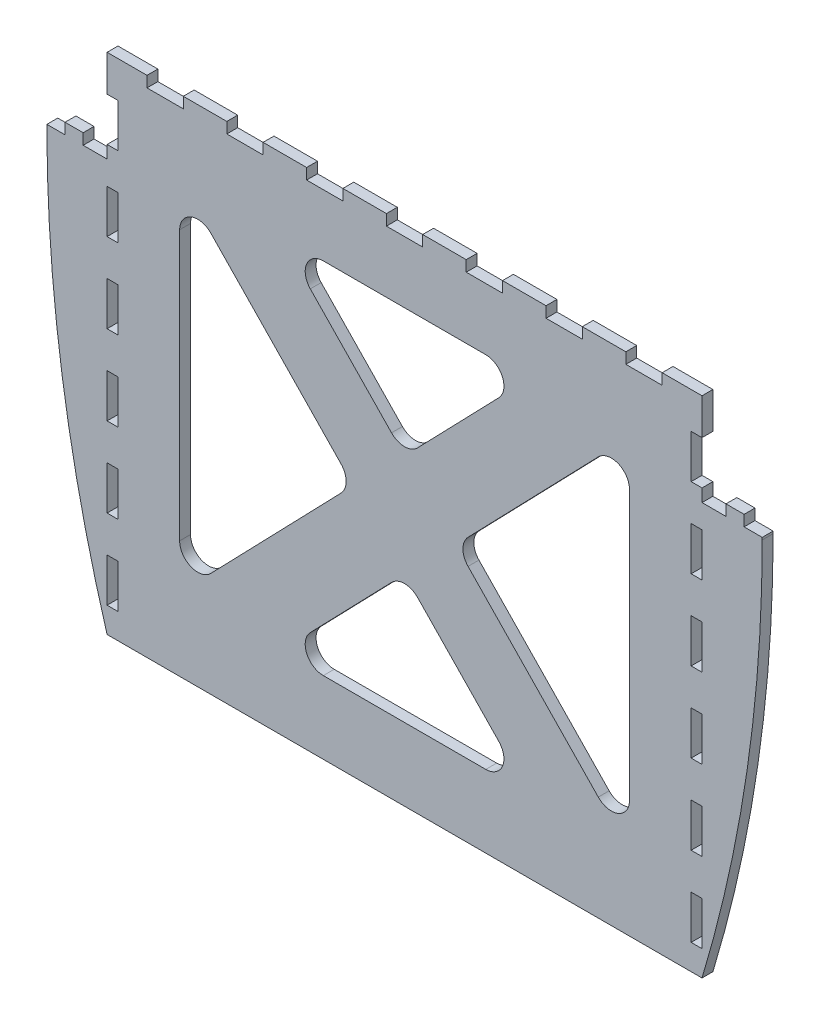
SolidWorks part; units mm, degrees
material "birch 3mm plywood"
ref_plane "Front Plane" through (0, 0, 0) normal (0, 0, 1) x (1, 0, 0)
ref_plane "Top Plane" through (0, 0, 0) normal (0, 1, 0) x (1, 0, 0)
ref_plane "Right Plane" through (0, 0, 0) normal (1, 0, 0) x (0, 0, -1)
sketch "Sketch1" plane through (0, 0, 152) normal (0, 0, 1) x (1, 0, 0)
  line L1 (-82, 69.5) -> (82, 69.5)
  line L2 (-82, 69.5) -> (-82, 44)
  line L3 (-82, -69.5) -> (82, -69.5)
  line L4 (82, 69.5) -> (82, 44)
  line L6 (-62, -37.1347) -> (-62, 37.1347)
  line L7 (-53.4053, 40.61) -> (-17.504, 3.4753)
  line L8 (-88.6, 47) -> (-93.6, 47)
  line L9 (-98.6, 44) -> (-98.6, 43.3771)
  line L10 (0, 69.5) -> (0, -69.5) construction
  line L12 (75, -62.5) -> (-75, -62.5) construction
  line L13 (75, 62.5) -> (75, -62.5) construction
  line L14 (-75, -62.5) -> (-75, 62.5) construction
  line L15 (-75, 62.5) -> (75, 62.5) construction
  line L18 (22.3929, 49.5) -> (-22.3929, 49.5)
  line L19 (-17.504, -3.4753) -> (-53.4053, -40.61)
  line L20 (-25.9877, 41.0247) -> (-3.5947, 17.8624)
  line L21 (3.5947, 17.8624) -> (25.9877, 41.0247)
  line L23 (53.4053, 40.61) -> (17.504, 3.4753)
  line L24 (62, -37.1347) -> (62, 37.1347)
  line L25 (17.504, -3.4753) -> (53.4053, -40.61)
  line L26 (-75, 0) -> (75, 0) construction
  line L27 (-25.9877, -41.0247) -> (-3.5947, -17.8624)
  line L28 (22.3929, -49.5) -> (-22.3929, -49.5)
  line L29 (3.5947, -17.8624) -> (25.9877, -41.0247)
  line L30 (0, 14.1442) -> (0, -14.1442) construction
  line L31 (-14.1442, 0) -> (14.1442, 0) construction
  line L32 (0, 14.1442) -> (0, -14.1442) construction
  line L33 (-93.6, 47) -> (-93.6, 44)
  line L34 (-93.6, 44) -> (-98.6, 44)
  line L35 (-88.6, 47) -> (-88.6, 44)
  line L36 (-88.6, 44) -> (-82, 44)
  line L37 (98.6, 44) -> (98.6, 43.3771)
  line L38 (93.6, 44) -> (98.6, 44)
  line L39 (93.6, 47) -> (93.6, 44)
  line L40 (88.6, 47) -> (93.6, 47)
  line L41 (88.6, 47) -> (88.6, 44)
  line L42 (88.6, 44) -> (82, 44)
  arc A0 (-53.4053, -40.61) -> (-62, -37.1347) centre (-57, -37.1347) cw
  arc A1 (-17.504, -3.4753) -> (-17.504, 3.4753) centre (-21.0988, 0) ccw
  arc A2 (-53.4053, 40.61) -> (-62, 37.1347) centre (-57, 37.1347) ccw
  arc A3 (25.9877, -41.0247) -> (22.3929, -49.5) centre (22.3929, -44.5) cw
  arc A4 (-25.9877, -41.0247) -> (-22.3929, -49.5) centre (-22.3929, -44.5) ccw
  arc A5 (-3.5947, -17.8624) -> (3.5947, -17.8624) centre (0, -21.3377) cw
  arc A6 (17.504, 3.4753) -> (17.504, -3.4753) centre (21.0988, 0) ccw
  arc A7 (53.4053, -40.61) -> (62, -37.1347) centre (57, -37.1347) ccw
  arc A8 (62, 37.1347) -> (53.4053, 40.61) centre (57, 37.1347) ccw
  arc A9 (-25.9877, 41.0247) -> (-22.3929, 49.5) centre (-22.3929, 44.5) cw
  arc A10 (25.9877, 41.0247) -> (22.3929, 49.5) centre (22.3929, 44.5) ccw
  arc A11 (3.5947, 17.8624) -> (-3.5947, 17.8624) centre (0, 21.3377) cw
  arc A12 (-98.6, 43.3771) -> (-82, -69.5) centre (293.4723, 43.3771) ccw
  arc A14 (98.6, 43.3771) -> (82, -69.5) centre (-293.4723, 43.3771) cw
  point P14 (0, 0)
  point P15 (0, 0)
  point P32 (-62, 49.5)
  point P35 (34.1815, -49.5)
  point P38 (-34.1815, -49.5)
  point P51 (-34.1815, 49.5)
  point P54 (34.1815, 49.5)
  point P77 (0, 0)
  dimension "D9" = 5
  dimension "D10" = 5
  dimension "D2" = 20
  dimension "D3" = 7
  dimension "D4" = 7
  dimension "D5" = 20
  dimension "D6" = 20
  dimension "D7" = 20
  dimension "D8" = 20
  dimension "D11" = 150
  dimension "D12" = 125
  dimension "D13" = 7
  dimension "D14" = 22.5
  dimension "D15" = 16.6
  dimension "D16" = 3
  dimension "D17" = 5
  dimension "D18" = 5
extrude "Boss-Extrude1" add sketch "Sketch1" along normal blind 3
sketch "Sketch2" plane through (0, 0, 155) normal (0, 0, 1) x (1, 0, 0)
  line L0 (0, 69.5) -> (0, -69.5) construction
  line L1 (17, 69.5) -> (17, 66.5)
  line L2 (-5, 69.5) -> (5, 69.5)
  line L3 (-5, 69.5) -> (-5, 66.5)
  line L4 (-82, 69.5) -> (-82, 44)
  line L5 (-82, -69.5) -> (82, -69.5)
  line L6 (82, 44) -> (82, 69.5)
  line L7 (82, 69.5) -> (-82, 69.5)
  line L8 (-82, 69.5) -> (-82, 44)
  line L9 (-82, -69.5) -> (82, -69.5)
  line L10 (82, 44) -> (82, 69.5)
  line L11 (82, 69.5) -> (-82, 69.5)
  line L12 (-5, 66.5) -> (5, 66.5)
  line L13 (5, 69.5) -> (5, 66.5)
  line L14 (17, 69.5) -> (27, 69.5)
  line L15 (27, 69.5) -> (27, 66.5)
  line L16 (17, 66.5) -> (27, 66.5)
  line L17 (39, 69.5) -> (39, 66.5)
  line L18 (39, 69.5) -> (49, 69.5)
  line L19 (49, 69.5) -> (49, 66.5)
  line L20 (39, 66.5) -> (49, 66.5)
  line L21 (61, 69.5) -> (61, 66.5)
  line L22 (61, 69.5) -> (71, 69.5)
  line L23 (71, 69.5) -> (71, 66.5)
  line L24 (61, 66.5) -> (71, 66.5)
  line L25 (-27, 69.5) -> (-27, 66.5)
  line L26 (-27, 69.5) -> (-17, 69.5)
  line L27 (-17, 69.5) -> (-17, 66.5)
  line L28 (-27, 66.5) -> (-17, 66.5)
  line L29 (-49, 69.5) -> (-49, 66.5)
  line L30 (-49, 69.5) -> (-39, 69.5)
  line L31 (-39, 69.5) -> (-39, 66.5)
  line L32 (-49, 66.5) -> (-39, 66.5)
  line L33 (-71, 69.5) -> (-71, 66.5)
  line L34 (-71, 69.5) -> (-61, 69.5)
  line L35 (-61, 69.5) -> (-61, 66.5)
  line L36 (-71, 66.5) -> (-61, 66.5)
  line L37 (-82, 37.5) -> (-82, 25.5)
  line L38 (-82, 59.5) -> (-79, 59.5)
  line L39 (-82, 59.5) -> (-82, 47.5)
  line L40 (-82, 47.5) -> (-79, 47.5)
  line L41 (-79, 59.5) -> (-79, 47.5)
  line L42 (-82, 37.5) -> (-79, 37.5)
  line L43 (-79, 37.5) -> (-79, 25.5)
  line L44 (-82, 25.5) -> (-79, 25.5)
  line L45 (-82, 15.5) -> (-82, 3.5)
  line L46 (-82, 15.5) -> (-79, 15.5)
  line L47 (-79, 15.5) -> (-79, 3.5)
  line L48 (-82, 3.5) -> (-79, 3.5)
  line L49 (-82, -6.5) -> (-82, -18.5)
  line L50 (-82, -6.5) -> (-79, -6.5)
  line L51 (-79, -6.5) -> (-79, -18.5)
  line L52 (-82, -18.5) -> (-79, -18.5)
  line L53 (-82, -28.5) -> (-82, -40.5)
  line L54 (-82, -28.5) -> (-79, -28.5)
  line L55 (-79, -28.5) -> (-79, -40.5)
  line L56 (-82, -40.5) -> (-79, -40.5)
  line L57 (-82, -50.5) -> (-82, -62.5)
  line L58 (-82, -50.5) -> (-79, -50.5)
  line L59 (-79, -50.5) -> (-79, -62.5)
  line L60 (-82, -62.5) -> (-79, -62.5)
  line L65 (82, -50.5) -> (79, -50.5)
  line L66 (79, -50.5) -> (79, -62.5)
  line L67 (82, -62.5) -> (79, -62.5)
  line L68 (82, -50.5) -> (82, -62.5)
  line L69 (82, -28.5) -> (79, -28.5)
  line L70 (79, -28.5) -> (79, -40.5)
  line L71 (82, -40.5) -> (79, -40.5)
  line L72 (82, -28.5) -> (82, -40.5)
  line L73 (82, -6.5) -> (79, -6.5)
  line L74 (79, -6.5) -> (79, -18.5)
  line L75 (82, -18.5) -> (79, -18.5)
  line L76 (82, -6.5) -> (82, -18.5)
  line L77 (82, 15.5) -> (79, 15.5)
  line L78 (79, 15.5) -> (79, 3.5)
  line L79 (82, 3.5) -> (79, 3.5)
  line L80 (82, 15.5) -> (82, 3.5)
  line L81 (82, 37.5) -> (79, 37.5)
  line L82 (79, 37.5) -> (79, 25.5)
  line L83 (82, 25.5) -> (79, 25.5)
  line L84 (82, 37.5) -> (82, 25.5)
  line L85 (82, 47.5) -> (79, 47.5)
  line L86 (79, 59.5) -> (79, 47.5)
  line L87 (82, 59.5) -> (79, 59.5)
  line L88 (82, 59.5) -> (82, 47.5)
  line L97 (-88.6, 47) -> (-93.6, 47)
  line L98 (-88.6, 47) -> (-93.6, 47)
  line L99 (-98.6, 44) -> (-98.6, 43.3771)
  line L100 (-98.6, 44) -> (-98.6, 43.3771)
  line L101 (98.6, 43.3771) -> (98.6, 44)
  line L103 (98.6, 43.3771) -> (98.6, 44)
  line L109 (-82, 44) -> (-88.6, 44)
  line L110 (-82, 44) -> (-88.6, 44)
  line L111 (-88.6, 44) -> (-88.6, 47)
  line L112 (-88.6, 44) -> (-88.6, 47)
  line L113 (-93.6, 47) -> (-93.6, 44)
  line L114 (-93.6, 47) -> (-93.6, 44)
  line L115 (-93.6, 44) -> (-98.6, 44)
  line L116 (-93.6, 44) -> (-98.6, 44)
  line L121 (98.6, 44) -> (93.6, 44)
  line L122 (98.6, 44) -> (93.6, 44)
  line L123 (93.6, 44) -> (93.6, 47)
  line L124 (93.6, 44) -> (93.6, 47)
  line L125 (93.6, 47) -> (88.6, 47)
  line L126 (93.6, 47) -> (88.6, 47)
  line L127 (88.6, 47) -> (88.6, 44)
  line L128 (88.6, 47) -> (88.6, 44)
  line L129 (88.6, 44) -> (82, 44)
  line L130 (88.6, 44) -> (82, 44)
  arc A2 (-98.6, 43.3771) -> (-82, -69.5) centre (293.4723, 43.3771) ccw
  arc A3 (-98.6, 43.3771) -> (-82, -69.5) centre (293.4723, 43.3771) ccw
  arc A4 (82, -69.5) -> (98.6, 43.3771) centre (-293.4723, 43.3771) ccw
  arc A6 (82, -69.5) -> (98.6, 43.3771) centre (-293.4723, 43.3771) ccw
  point P10 (0, 66.5)
  line M64 (82, 44) -> (82, 69.5)
  line M65 (82, 69.5) -> (-82, 69.5)
  dimension "D2" = 10
  dimension "D3" = 3
  dimension "D6" = 12
  dimension "D7" = 12
  dimension "D8" = 3
  dimension "D9" = 12
  dimension "D10" = 10
  dimension "D12" = 10
  dimension "D1" = 0
  dimension "D4" = 4
  dimension "D5" = 4
  dimension "D11" = 6
extrude "Cut-Extrude1" cut sketch "Sketch2" against normal blind 10 contours L8 L44 L43 L42 | L33 L36 L35 L11 | L29 L32 L31 M65 | L25 L28 L27 L11 | L0 L12 L13 M65 | L0 L11 L3 L12 | L1 L16 L15 L11 | L17 L20 L19 L11 | L21 L24 L23 L11 | L87 L86 L85 M64 | L79 L77 L78 M64 | L75 L10 L73 L74 | L71 L69 L70 M64 | L67 L10 L65 L66 | L41 L40 L39 L38 | L47 L48 L45 L46 | L51 L52 L49 L50 | L55 L56 L53 L54 | L59 L60 L57 L58 | L82 L83 L84 L81 region at (2.5, 68, 155) region at (-2.5, 68, 155) region at (-22, 68, 155) region at (22, 68, 155) region at (-44, 68, 155) region at (44, 68, 155) region at (-66, 68, 155) region at (66, 68, 155) region at (80.5, 53.5, 155) region at (-80.5, 31.5, 155) region at (80.5, -56.5, 155) region at (80.5, -34.5, 155) region at (80.5, -12.5, 155) region at (80.5, 9.5, 155)
